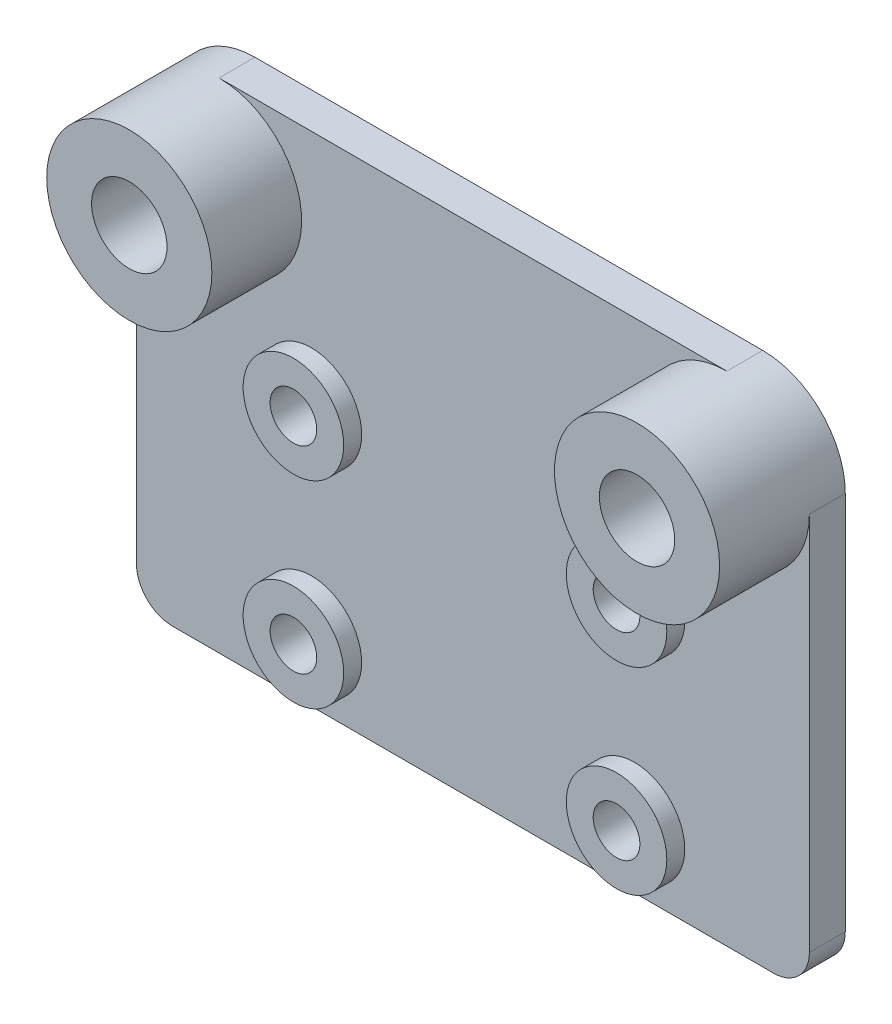
SolidWorks part; units mm, degrees
material "ABS"
ref_plane "Plan de face" through (0, 0, 0) normal (0, 0, 1) x (1, 0, 0)
ref_plane "Plan de dessus" through (0, 0, 0) normal (0, 1, 0) x (1, 0, 0)
ref_plane "Plan de droite" through (0, 0, 0) normal (1, 0, 0) x (0, 0, -1)
sketch "Esquisse1" plane through (0, 0, 0) normal (0, 0, 1) x (1, 0, 0)
  line L0 (-14.1421, 14.1421) -> (14.1421, 14.1421) construction
  line L1 (9, 5.5) -> (-9, 5.5) construction
  line L2 (9, 5.5) -> (9, -5.5) construction
  line L3 (9, -5.5) -> (-9, -5.5) construction
  line L4 (-9, 5.5) -> (-9, -5.5) construction
  line L5 (9, 5.5) -> (-9, -5.5) construction
  line L6 (9, -5.5) -> (-9, 5.5) construction
  line L7 (14.1421, 14.1421) -> (14.1421, -14.1421) construction
  line L8 (14.1421, -14.1421) -> (-14.1421, -14.1421) construction
  line L9 (-14.1421, -14.1421) -> (-14.1421, 14.1421) construction
  circle A0 centre (0, 0) radius 20 construction
  circle A1 centre (-14.1421, 14.1421) radius 2.1
  circle A2 centre (14.1421, 14.1421) radius 2.1
  circle A3 centre (14.1421, -14.1421) radius 2.1 construction
  circle A4 centre (-14.1421, -14.1421) radius 2.1 construction
  circle A5 centre (0, 0) radius 25
  circle A6 centre (-9, 5.5) radius 1.3
  circle A7 centre (-9, -5.5) radius 1.3
  circle A8 centre (9, 5.5) radius 1.3
  circle A9 centre (9, -5.5) radius 1.3
  point P0 (0, 0)
  dimension "D3" = 40
  dimension "D4" = 4.2
  dimension "D5" = 4.2
  dimension "D6" = 4.2
  dimension "D7" = 4.2
  dimension "D8" = 50
  dimension "D9" = 2.6
  dimension "D10" = 2.6
  dimension "D11" = 2.6
  dimension "D12" = 2.6
  dimension "D1" = 18
  dimension "D2" = 11
extrude "Boss.-Extru.1" add sketch "Esquisse1" along normal blind 2
sketch "Esquisse2" plane through (0, 0, 2) normal (0, 0, 1) x (1, 0, 0)
  line L0 (0, -14) -> (0, 0) construction
  line L1 (11, -19) -> (-11, -19)
  line L2 (11, -19) -> (11, -9)
  line L3 (11, -9) -> (-11, -9)
  line L4 (-11, -19) -> (-11, -9)
  line L5 (11, -19) -> (-11, -9) construction
  line L6 (11, -9) -> (-11, -19) construction
  point P0 (0, -14)
  dimension "D1" = 9
  dimension "D2" = 22
  dimension "D3" = 10
extrude "Enlèv. mat.-Extru.1" cut sketch "Esquisse2" against normal blind 2
sketch "Esquisse3" plane through (0, 0, 2) normal (0, 0, 1) x (1, 0, 0)
  circle A2 centre (-9, -5.5) radius 1.3 construction
  circle A3 centre (9, -5.5) radius 1.3 construction
  circle A4 centre (9, 5.5) radius 1.3 construction
  circle A5 centre (-14.1421, 14.1421) radius 2.1 construction
  circle A6 centre (-9, 5.5) radius 1.3 construction
  circle A7 centre (14.1421, -14.1421) radius 2.1
  circle A8 centre (-14.1421, -14.1421) radius 2.1
  circle A9 centre (-9, -5.5) radius 1.3
  circle A10 centre (9, -5.5) radius 1.3
  circle A11 centre (9, 5.5) radius 1.3
  circle A12 centre (-14.1421, 14.1421) radius 2.1
  circle A13 centre (-9, 5.5) radius 1.3
  circle A14 centre (-9, -5.5) radius 2.8
  circle A15 centre (9, -5.5) radius 2.8
  circle A16 centre (9, 5.5) radius 2.8
  circle A17 centre (-9, 5.5) radius 2.8
  circle A18 centre (-14.1421, 14.1421) radius 4.6
  circle A19 centre (14.1421, -14.1421) radius 3.6
  circle A20 centre (-14.1421, -14.1421) radius 3.6
  circle A21 centre (14.1421, 14.1421) radius 2.1 construction
  circle A22 centre (14.1421, 14.1421) radius 2.1
  circle A23 centre (14.1421, 14.1421) radius 4.6
  point P40 (0, 0)
  dimension "D1" = 1.5
  dimension "D2" = 2.5
  dimension "D3" = 1.5
  dimension "D4" = 2.5
extrude "Boss.-Extru.2" add sketch "Esquisse3" along normal blind 1
sketch "Esquisse4" plane through (0, 0, 0) normal (0, 0, -1) x (-1, 0, 0)
  line L0 (-14.1421, 18.7421) -> (14.1421, 18.7421)
  line L1 (-18.7421, 14.1421) -> (-18.7421, -9)
  line L2 (18.7421, 14.1421) -> (18.7421, -9)
  line L4 (18.7421, -9) -> (-18.7421, -9)
  circle A0 centre (-14.1421, 14.1421) radius 4.6 construction
  circle A1 centre (14.1421, 14.1421) radius 4.6 construction
  circle A4 centre (-14.1421, 14.1421) radius 4.6 construction
  arc A5 (-14.1421, 18.7421) -> (-18.7421, 14.1421) centre (-14.1421, 14.1421) ccw
  circle A6 centre (14.1421, 14.1421) radius 4.6 construction
  arc A7 (18.7421, 14.1421) -> (14.1421, 18.7421) centre (14.1421, 14.1421) ccw
  dimension "D1" = 9
extrude "Enlèv. mat.-Extru.2" cut sketch "Esquisse4" against normal through all flip side to cut
fillet "Congé1" radius 2 2 edges at (18.7421, -9, 1) (-18.7421, -9, 1)
sketch "Esquisse5" plane through (0, 0, 3) normal (0, 0, 1) x (1, 0, 0)
  circle A2 centre (14.1421, 14.1421) radius 4.6 construction
  circle A3 centre (-14.1421, 14.1421) radius 4.6 construction
  circle A4 centre (-14.1421, -14.1421) radius 3.6 construction
  circle A5 centre (14.1421, -14.1421) radius 3.6 construction
  circle A6 centre (14.1421, 14.1421) radius 4.6
  circle A7 centre (-14.1421, 14.1421) radius 4.6
  circle A9 centre (14.1421, 14.1421) radius 2.1 construction
  circle A11 centre (-14.1421, 14.1421) radius 2.1 construction
  circle A12 centre (14.1421, -14.1421) radius 2.1 construction
  circle A13 centre (14.1421, 14.1421) radius 2.1
  circle A14 centre (-14.1421, -14.1421) radius 2.1 construction
  circle A15 centre (-14.1421, 14.1421) radius 2.1
extrude "Boss.-Extru.3" add sketch "Esquisse5" along normal blind 4
